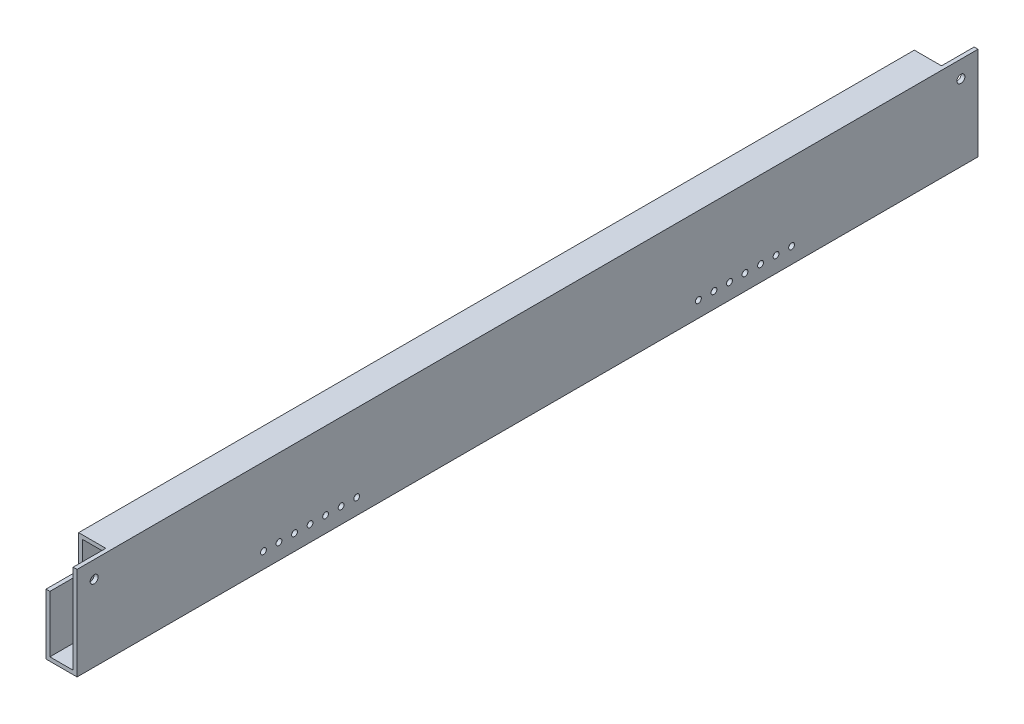
SolidWorks part; units mm, degrees
ref_plane "Front Plane" through (0, 0, 0) normal (0, 0, 1) x (1, 0, 0)
ref_plane "Top Plane" through (0, 0, 0) normal (0, 1, 0) x (1, 0, 0)
ref_plane "Right Plane" through (0, 0, 0) normal (1, 0, 0) x (0, 0, -1)
sketch "Sketch1" plane through (0, 0, 0) normal (0, 0, 1) x (1, 0, 0)
  line L1 (-12.7, -38.1) -> (12.7, -38.1)
  line L2 (-12.7, -38.1) -> (-12.7, 38.1)
  line L3 (-12.7, 38.1) -> (12.7, 38.1)
  line L4 (12.7, -38.1) -> (12.7, 38.1)
  line L5 (-12.7, -38.1) -> (12.7, 38.1) construction
  line L6 (-12.7, 38.1) -> (12.7, -38.1) construction
  point P0 (0, 0)
  dimension "D1" = 25.4
  dimension "D2" = 76.2
extrude "Boss-Extrude1" add sketch "Sketch1" along normal mid plane 736.6
shell "Shell1" thickness 3.175 removed face at (0, 0, -368.3) removed face at (0, 0, 368.3)
sketch "Sketch3" plane through (12.7, 0, 0) normal (1, 0, 0) x (0, 0, -1)
  line L0 (368.3, -38.1) -> (368.3, 38.1) construction
  line L1 (-368.3, -38.1) -> (368.3, -38.1) construction
  line L2 (0, -53.276) -> (0, 47.534) construction
  circle A0 centre (215.9, -25.1959) radius 2.3813
  circle A1 centre (203.2, -25.1959) radius 2.3813
  circle A2 centre (190.5, -25.1959) radius 2.3813
  circle A3 centre (177.8, -25.1959) radius 2.3813
  circle A4 centre (165.1, -25.1959) radius 2.3813
  circle A5 centre (152.4, -25.1959) radius 2.3813
  circle A6 centre (139.7, -25.1959) radius 2.3813
  circle A7 centre (-139.7, -25.1959) radius 2.3813
  circle A8 centre (-152.4, -25.1959) radius 2.3813
  circle A9 centre (-165.1, -25.1959) radius 2.3813
  circle A10 centre (-203.2, -25.1959) radius 2.3813
  circle A11 centre (-177.8, -25.1959) radius 2.3813
  circle A12 centre (-215.9, -25.1959) radius 2.3813
  circle A13 centre (-190.5, -25.1959) radius 2.3813
  dimension "D1" = 4.7625
  dimension "D3" = 12.7
  dimension "D4" = 12.7
  dimension "D5" = 12.7
  dimension "D6" = 12.7
  dimension "D7" = 12.7
  dimension "D8" = 12.7
  dimension "D9" = 12.9041
  dimension "D2" = 152.4
extrude "Cut-Extrude2" cut sketch "Sketch3" against normal up to next
sketch "Sketch4" plane through (-12.7, 0, 0) normal (-1, 0, 0) x (0, 0, 1)
  line L1 (-368.3, 38.1) -> (-341.63, 38.1)
  line L2 (-368.3, 38.1) -> (-368.3, 11.43)
  line L3 (-368.3, 11.43) -> (-341.63, 11.43)
  line L4 (-341.63, 38.1) -> (-341.63, 11.43)
  line L5 (368.3, 38.1) -> (341.63, 38.1)
  line L6 (368.3, 38.1) -> (368.3, 11.43)
  line L7 (368.3, 11.43) -> (341.63, 11.43)
  line L8 (341.63, 38.1) -> (341.63, 11.43)
  dimension "D1" = 26.67
  dimension "D2" = 26.67
  dimension "D3" = 26.67
  dimension "D4" = 26.67
extrude "Cut-Extrude3" cut sketch "Sketch4" against normal blind 22.225
sketch "Sketch5" plane through (9.525, 0, 0) normal (-1, 0, 0) x (0, 0, 1)
  line L0 (-341.63, 38.1) -> (-368.3, 38.1) construction
  line L1 (-368.3, -34.925) -> (-368.3, 38.1) construction
  line L2 (368.3, 38.1) -> (341.63, 38.1) construction
  line L4 (368.3, -34.925) -> (368.3, 38.1) construction
  circle A0 centre (-354.33, 24.13) radius 3.25
  circle A1 centre (354.33, 24.13) radius 3.25
  point P12 (368.3, 20.5149)
  dimension "D3" = 6.5
  dimension "D4" = 6.5
  dimension "D6" = 13.97
  dimension "D1" = 13.97
  dimension "D2" = 13.97
  dimension "D5" = 13.97
extrude "Cut-Extrude4" cut sketch "Sketch5" against normal blind 22.225
equation "\"robotwidth\"= 29in"
equation "\"D1@Boss-Extrude1\"=\"robotwidth\""
